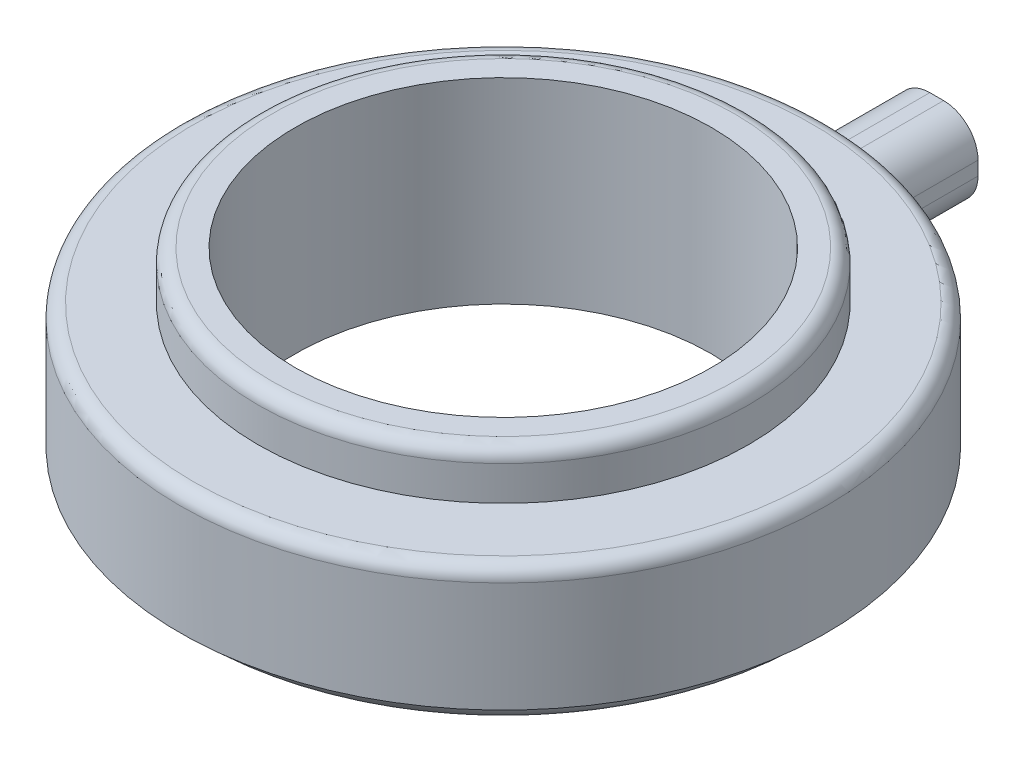
SolidWorks part; units mm, degrees
material "SKD11淬火HRC56-60"
ref_plane "前基準面" through (0, 0, 0) normal (0, 0, 1) x (1, 0, 0)
ref_plane "上基準面" through (0, 0, 0) normal (0, 1, 0) x (1, 0, 0)
ref_plane "右基準面" through (0, 0, 0) normal (1, 0, 0) x (0, 0, -1)
sketch "草图1" plane through (0, 0, 0) normal (0, 1, 0) x (1, 0, 0)
  circle A0 centre (0, 0) radius 47
  dimension "D1" = 94
extrude "凸台-拉伸1" add sketch "草图1" along normal blind 21.5
sketch "草图2" plane through (0, 21.5, 0) normal (0, 1, 0) x (1, 0, 0)
  circle A0 centre (0, 0) radius 35.65
  dimension "D1" = 71.3
extrude "凸台-拉伸2" add sketch "草图2" along normal blind 7
sketch "草图3" plane through (0, 28.5, 0) normal (0, 1, 0) x (1, 0, 0)
  circle A0 centre (0, 0) radius 30.25
  dimension "D1" = 60.5
extrude "切除-拉伸1" cut sketch "草图3" against normal through all
fillet "圆角1" radius 2 2 edges at (0, 28.5, 35.65) (0, 21.5, 47)
sketch "草图4" plane through (0, 0, 0) normal (1, 0, 0) x (0, 0, -1)
  line L0 (63, 10) -> (-40.6111, 10) construction
  line L1 (-40.6111, 16) -> (63, 16)
  line L2 (-40.6111, 16) -> (-40.6111, 4)
  line L3 (-40.6111, 4) -> (63, 4)
  line L4 (63, 16) -> (63, 4)
  line L6 (47, 0) -> (47, 19.5) construction
  line L7 (-47, 0) -> (47, 0) construction
  dimension "D1" = 12
  dimension "D2" = 10
  dimension "D3" = 16
extrude "凸台-拉伸3" add sketch "草图4" along normal blind 6 and the other way blind 6
sketch "草图6" plane through (0, 16, 0) normal (0, 1, 0) x (1, 0, 0)
  line L2 (-6, 29.649) -> (-6, -29.649)
  line L3 (6, -29.649) -> (6, 29.649)
  line L4 (-6, 29.649) -> (-6, -29.649)
  line L5 (6, -29.649) -> (6, 29.649)
  arc A2 (6, 29.649) -> (-6, 29.649) centre (0, 0) ccw
  arc A3 (-6, -29.649) -> (6, -29.649) centre (0, 0) ccw
  arc A4 (6, 29.649) -> (-6, 29.649) centre (0, 0) ccw
  arc A5 (-6, -29.649) -> (6, -29.649) centre (0, 0) ccw
  dimension "D1" = 0
extrude "切除-拉伸3" cut sketch "草图6" against normal through all
fillet "圆角2" radius 5 4 edges at (-6, 16, -54.8077) (-6, 4, -54.8077) (6, 4, -54.8077) (6, 16, -54.8077)
sketch "草图5" plane through (0, 0, -63) normal (0, 0, -1) x (-1, 0, 0)
  line L0 (0, 16) -> (0, 4) construction
  line L1 (1, 16) -> (-1, 16) construction
  line L2 (1, 4) -> (-1, 4) construction
  circle A0 centre (0, 10) radius 3.75
  dimension "D1" = 7.5
extrude "切除-拉伸2" cut sketch "草图5" against normal blind 6
sketch "草图7" plane through (0, 0, 0) normal (0, -1, 0) x (1, 0, 0)
  circle A0 centre (0, 0) radius 45
  circle A2 centre (0, 0) radius 47
  circle A3 centre (0, 0) radius 47
  dimension "D1" = 90
  dimension "D2" = 0
extrude "切除-拉伸4" cut sketch "草图7" against normal blind 3.5
fillet "圆角3" radius 3 1 edges at (0, 0, -45)
